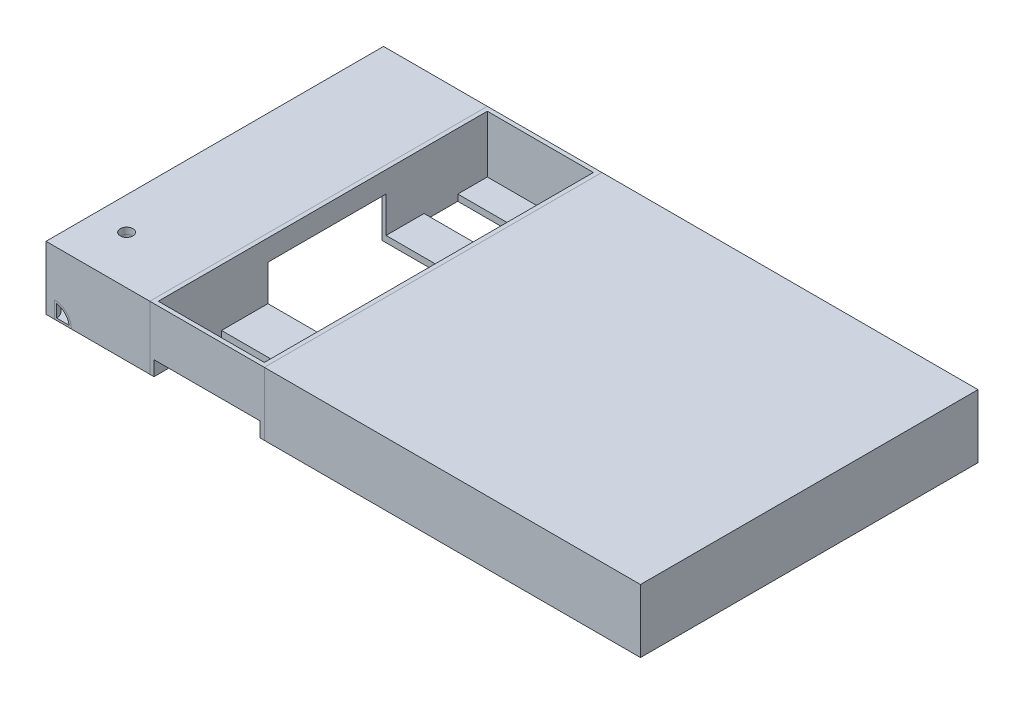
SolidWorks part; units mm, degrees
note: The reader was unsure of these and kept them because the rebuilt part matched: shared geometry of "Sketch11<3>", "Sketch33<2>", "Sketch47<2>".
ref_plane "Front Plane" through (0, 0, 0) normal (0, 0, 1) x (1, 0, 0)
ref_plane "Top Plane" through (0, 0, 0) normal (0, 1, 0) x (1, 0, 0)
ref_plane "Right Plane" through (0, 0, 0) normal (1, 0, 0) x (0, 0, -1)
sketch3d "3DSketch2"
  line L1 (-44.35, 29.25, -28.4) -> (-20.2, 23.2287, -28.4) construction
  dimension "D1" = 0
sketch "Sketch1" plane through (0, 0, 0) normal (0, 1, 0) x (1, 0, 0)
  line L1 (-70.45, -40) -> (70.45, -40)
  line L2 (-70.45, -40) -> (-70.45, 40)
  line L3 (-70.45, 40) -> (70.45, 40)
  line L4 (70.45, -40) -> (70.45, 40)
  line L5 (-70.45, -40) -> (70.45, 40) construction
  line L6 (-70.45, 40) -> (70.45, -40) construction
  point P0 (0, 0)
  dimension "D1" = 80
  dimension "D2" = 140.9
extrude "Boss-Extrude1" add sketch "Sketch1" along normal blind 15
shell "Shell3" thickness 1.5
sketch "Sketch4" plane through (-70.45, 0, 0) normal (-1, 0, 0) x (0, 0, 1)
  line L0 (-34.38, 1.6) -> (-28.48, 1.6) construction
  line L1 (-34.38, 3.3) -> (-28.48, 3.3)
  line L2 (-34.38, -0.1) -> (-28.48, -0.1)
  line L3 (-40, 15) -> (-40, 0) construction
  arc A0 (-34.38, 3.3) -> (-34.38, -0.1) centre (-34.38, 1.6) ccw
  arc A1 (-28.48, -0.1) -> (-28.48, 3.3) centre (-28.48, 1.6) ccw
  point P2 (-31.43, 1.6)
  dimension "D1" = 8.57
  dimension "D2" = 5.9
  dimension "D3" = 3.4
extrude "Cut-Extrude2" cut sketch "Sketch4" against normal blind 1.5
sketch "Sketch6" plane through (-70.45, 0, 0) normal (-1, 0, 0) x (0, 0, 1)
  line L0 (-27.9055, 0) -> (40, 0) construction
  line L1 (-24.4, 7.3) -> (-10.75, 7.3)
  line L2 (-24.4, 7.3) -> (-24.4, 0)
  line L3 (-24.4, 0) -> (-10.75, 0)
  line L4 (-10.75, 7.3) -> (-10.75, 0)
  line L5 (-24.4, 7.3) -> (-10.75, 0) construction
  line L6 (-24.4, 0) -> (-10.75, 7.3) construction
  line L8 (-40, 15) -> (-40, 0) construction
  point P6 (-17.575, 3.65)
  dimension "D1" = 7.3
  dimension "D2" = 13.65
  dimension "D3" = 0
  dimension "D4" = 22.425
extrude "Cut-Extrude3" cut sketch "Sketch6" against normal blind 1.5
sketch "Sketch9" plane through (-70.45, 0, 0) normal (-1, 0, 0) x (0, 0, 1)
  line L0 (-27.9055, 0) -> (-24.4, 0) construction
  line L1 (-25.4, 0) -> (-9.75, 0)
  line L2 (-25.4, 0) -> (-25.4, 1)
  line L3 (-25.4, 1) -> (-9.75, 1)
  line L4 (-9.75, 0) -> (-9.75, 1)
  line L5 (-10.75, 0) -> (-10.75, 7.3) construction
  line L7 (-24.4, 7.3) -> (-24.4, 0) construction
  dimension "D1" = 1
  dimension "D2" = 1
  dimension "D3" = 1
extrude "Boss-Extrude2" add sketch "Sketch9" along normal blind 1.5
sketch "Sketch11" plane through (0, 15, 0) normal (0, 1, 0) x (1, 0, 0)
  line L1 (-70.45, 40) -> (-70.45, -40) construction
  circle A0 centre (-62.75, -28.6) radius 1.5
  dimension "D1" = 7.7
extrude "Boss-Extrude10" add sketch "Sketch11" against normal blind 11
extrude "Cut-Extrude10" cut sketch "Sketch11<3>" against normal blind 1.5
sketch "Sketch11<3>" plane through (0, 15, 0) normal (0, 1, 0) x (1, 0, 0) same geometry as "Sketch11"
shell "Shell9" thickness 1
sketch "Sketch33" plane through (0, 0, 40) normal (0, 0, 1) x (1, 0, 0)
  line L3 (-70.45, 0) -> (70.45, 0) construction
  line L6 (-68.45, 4) -> (-68.45, 0)
  line L7 (-68.45, 0) -> (-64.45, 0)
  arc A2 (-68.45, 4) -> (-64.45, 0) centre (-68.45, 0) cw
  dimension "D1" = 2
revolve "Cut-Revolve4" cut sketch "Sketch33" angle 90 about axis through (-70.45, 15, 40) along (0, -1, 0)
revolve "Revolve3" add sketch "Sketch33<2>" angle 90 about axis through (-70.45, 15, 40) along (0, -1, 0)
sketch "Sketch33<2>" plane through (0, 0, 40) normal (0, 0, 1) x (1, 0, 0) same geometry as "Sketch33"
shell "Shell14" thickness 0.5
sketch "Sketch45" plane through (4.2704, 17.1276, 0) normal (-0.2419, -0.9703, 0) x (-0.9703, 0.2419, 0)
  line L5 (-111.6083, -40) -> (91.6176, -40)
  line L6 (-111.6083, -40) -> (-111.6083, 40)
  line L7 (-111.6083, 40) -> (91.6176, 40)
  line L8 (91.6176, -40) -> (91.6176, 40)
sketch "Sketch47" plane through (0, 0, 40) normal (0, 0, 1) x (1, 0, 0)
  line L1 (-45.85, 0) -> (-18.7, 0)
  line L2 (-45.85, 0) -> (-45.85, 15)
  line L3 (-45.85, 15) -> (-18.7, 15)
  line L4 (-18.7, 0) -> (-18.7, 15)
  line L5 (-70.45, 15) -> (-70.45, 0) construction
  line L6 (-64.45, 0) -> (70.45, 0) construction
  dimension "D1" = 27.15
  dimension "D2" = 24.6
  dimension "D3" = 0
extrude "Cut-Extrude15" cut sketch "Sketch47" against normal through all
extrude "Boss-Extrude12" add sketch "Sketch47<2>" against normal blind 80 separate body
sketch "Sketch47<2>" plane through (0, 0, 40) normal (0, 0, 1) x (1, 0, 0) same geometry as "Sketch47"
shell "Shell15" thickness 1
sketch "Sketch52" plane through (0, 0, 39) normal (0, 0, -1) x (-1, 0, 0)
  line L0 (44.85, 15) -> (44.85, 1.5) construction
  line L1 (19.7, 0) -> (44.85, 0)
  line L2 (19.7, 0) -> (19.7, 3.5)
  line L3 (19.7, 3.5) -> (44.85, 3.5)
  line L4 (44.85, 0) -> (44.85, 3.5)
  line L5 (44.85, 15) -> (44.85, 1.5) construction
  line L6 (0.275, 14.9142) -> (-24.875, 14.9142) construction
  dimension "D1" = 25.15
  dimension "D2" = 11.4142
extrude "Cut-Extrude21" cut sketch "Sketch52" against normal blind 1
sketch "Sketch54" plane through (-44.85, 0, 0) normal (1, 0, 0) x (0, 0, -1)
  line L0 (-39, 0) -> (-40, 0) construction
  line L5 (15, 10) -> (-13, 10)
  line L6 (15, 10) -> (15, 0)
  line L7 (15, 0) -> (-13, 0)
  line L8 (-13, 10) -> (-13, 0)
  line L9 (15, 10) -> (-13, 0) construction
  line L10 (15, 0) -> (-13, 10) construction
  line L12 (40, 15) -> (40, 0) construction
  line L13 (-40, 15) -> (-40, 0) construction
  point P0 (1, 5)
  dimension "D1" = 10
  dimension "D2" = 25
  dimension "D3" = 27
extrude "Cut-Extrude22" cut sketch "Sketch54" against normal blind 1
sketch "Sketch55" plane through (0, 1.5, 0) normal (0, 1, 0) x (1, 0, 0)
  line L0 (-44.85, -13) -> (-44.85, -39) construction
  line L1 (-19.7, -39) -> (-44.85, -39)
  line L2 (-19.7, -39) -> (-19.7, -24)
  line L3 (-19.7, -24) -> (-44.85, -24)
  line L4 (-44.85, -39) -> (-44.85, -24)
  line L5 (-44.85, 15) -> (-44.85, -13) construction
  line L6 (-44.85, -13) -> (-19.7, -13)
  line L7 (-44.85, -13) -> (-44.85, 15)
  line L8 (-44.85, 15) -> (-19.7, 15)
  line L9 (-19.7, -13) -> (-19.7, 15)
  line L10 (-19.7, 39) -> (-19.7, -39) construction
  line L11 (-44.85, 39) -> (-44.85, 15) construction
  line L12 (-44.85, 32) -> (-19.7, 32)
  line L13 (-44.85, 32) -> (-44.85, 24)
  line L14 (-44.85, 24) -> (-19.7, 24)
  line L15 (-19.7, 32) -> (-19.7, 24)
  line L16 (-45.85, 40) -> (-18.7, 40) construction
  line L19 (-64.45, -40) -> (-45.85, -40) construction
  line L20 (-45.85, 40) -> (-70.45, 40) construction
  dimension "D1" = 8
  dimension "D2" = 16
  dimension "D3" = 25
  dimension "D4" = 16
  dimension "D5" = 53
extrude "Cut-Extrude23" cut sketch "Sketch55" against normal blind 1.5
